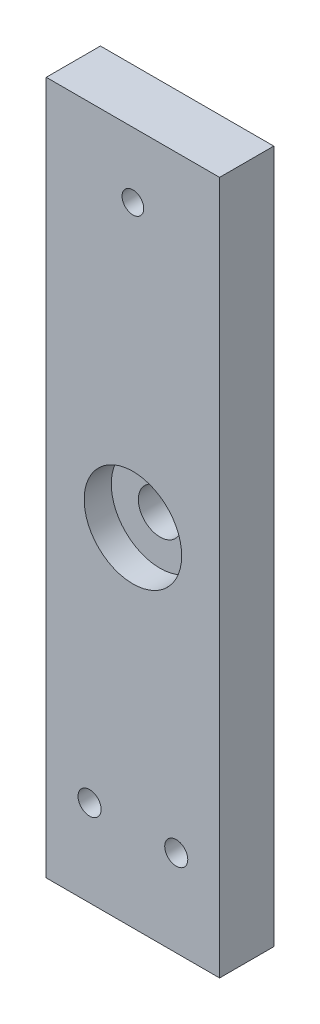
SolidWorks part; units mm, degrees
ref_plane "Front Plane" through (0, 0, 0) normal (0, 0, 1) x (1, 0, 0)
ref_plane "Top Plane" through (0, 0, 0) normal (0, 1, 0) x (1, 0, 0)
ref_plane "Right Plane" through (0, 0, 0) normal (1, 0, 0) x (0, 0, -1)
sketch "Sketch1" plane through (0, 0, 0) normal (0, 0, 1) x (1, 0, 0)
  line L0 (25.4, -25.4) -> (25.4, 25.4) construction
  line L1 (-25.4, -25.4) -> (25.4, -25.4)
  line L2 (-25.4, -25.4) -> (-25.4, 177.8)
  line L3 (-25.4, 177.8) -> (25.4, 177.8)
  line L4 (25.4, -25.4) -> (25.4, 177.8)
  dimension "D1" = 203.2
extrude "Boss-Extrude1" add sketch "Sketch1" along normal blind 15.875 contours L3 L4 L1 L2
sketch "Sketch2" plane through (0, 0, 15.875) normal (0, 0, 1) x (1, 0, 0)
  circle A0 centre (-12.7, 0) radius 3.3782 construction
  circle A1 centre (12.7, 0) radius 3.3782 construction
  circle A2 centre (-12.7, 0) radius 3.3782
  circle A3 centre (12.7, 0) radius 3.3782
extrude "Cut-Extrude1" cut sketch "Sketch2" against normal through all
sketch "Sketch5" plane through (0, 0, 0) normal (0, 0, -1) x (-1, 0, 0)
  line L0 (25.4, 177.8) -> (-25.4, 177.8) construction
  circle A0 centre (0, 158.75) radius 6.35
  circle A1 centre (0, 76.2) radius 6.35
  point P8 (0, 177.8)
  dimension "D2" = 12.7
  dimension "D3" = 12.7
  dimension "D1" = 82.55
  dimension "D4" = 19.05
extrude "Cut-Extrude2" cut sketch "Sketch5" against normal blind 6.35 contours A0
hole_wizard "1/4 (0.25) Diameter Hole1" positions "Sketch6" profile "Sketch7" hole size "1/4" standard "ANSI Inch" end condition through all
sketch "Sketch6" plane through (0, 0, 6.35) normal (0, 0, -1) x (-1, 0, 0)
  point P0 (0, 158.75)
sketch "Sketch7" plane through (0, 158.75, 6.35) normal (1, 0, 0) x (0, 1, 0)
  line L0 (0, 0) -> (0, 9.525)
  line L1 (0, 9.525) -> (3.175, 9.525)
  line L2 (3.175, 9.525) -> (3.175, 0)
  line L5 (3.175, 0) -> (0, 0)
  line L11 (0, -6.35) -> (0, 107.95) construction
  dimension "Thru Hole Dia." = 6.35
  dimension "Thru Hole Depth" = 9.525
extrude "Cut-Extrude3" cut sketch "Sketch5<3>" against normal through all contours A1 region at (0, 76.2, 0)
sketch "Sketch5<3>" plane through (0, 0, 0) normal (0, 0, -1) x (-1, 0, 0) same geometry as "Sketch5"
sketch "Sketch10" plane through (0, 0, 15.875) normal (0, 0, 1) x (1, 0, 0)
  circle A0 centre (0, 76.2) radius 6.35 construction
  circle A1 centre (0, 76.2) radius 6.35
  circle A2 centre (0, 76.2) radius 14.2875
  dimension "D1" = 28.575
extrude "Cut-Extrude4" cut sketch "Sketch10" against normal blind 7.9375
equation "\"UprightHeight\"= 8"
equation "\"D1@Sketch1\"=\"UprightHeight\""
equation "\"UprightThickness\"=0.625"
equation "\"D1@Boss-Extrude1\"=\"UprightThickness\""
equation "\"Shaft2Shaft\"=3.25"
equation "\"D1@Sketch5\"=\"Shaft2Shaft\""
equation "\"ShaftDia\"=0.5"
equation "\"D2@Sketch5\"=\"ShaftDia\""
equation "\"D3@Sketch5\"=\"ShaftDia\""
equation "\"ShaftClearance\"=0.75"
equation "\"D4@Sketch5\"=\"ShaftClearance\""
equation "\"BearingOD\"=1.125"
equation "\"D1@Sketch10\"=\"BearingOD\""
equation "\"BearingDepth\"=0.3125"
equation "\"D1@Cut-Extrude4\"=\"BearingDepth\""
